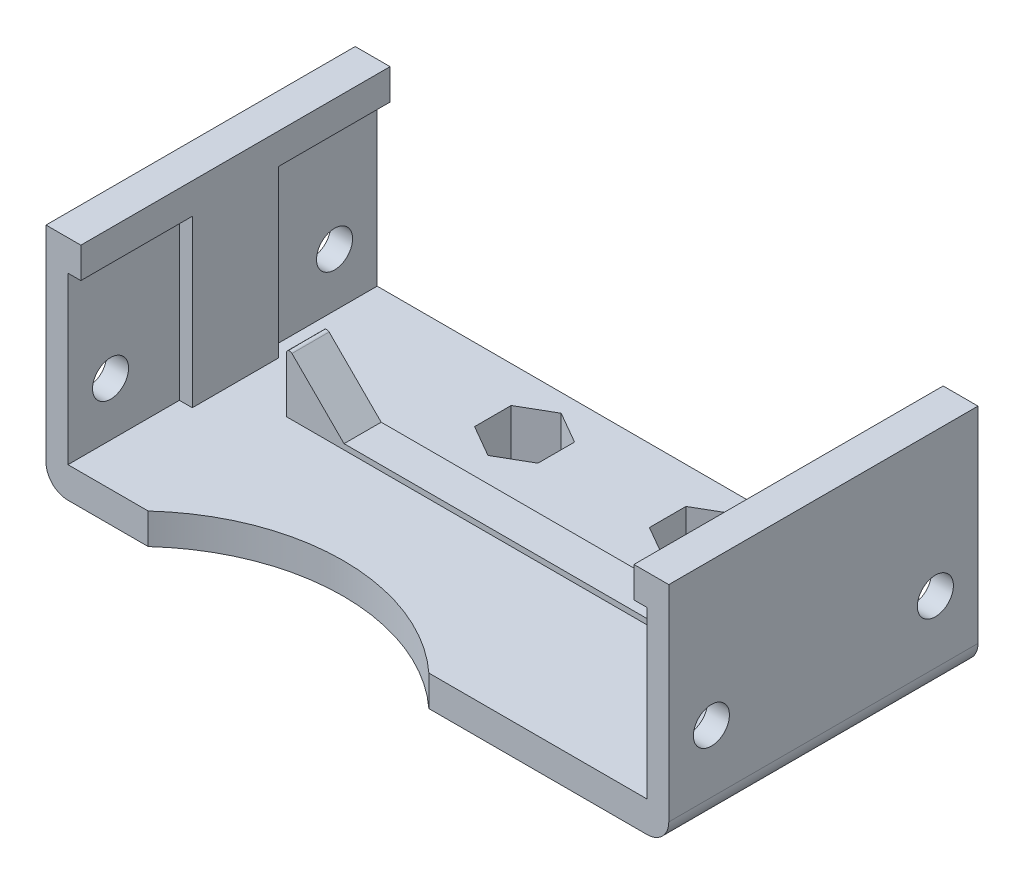
SolidWorks part; units mm, degrees
ref_plane "Front Plane" through (0, 0, 0) normal (0, 0, 1) x (1, 0, 0)
ref_plane "Top Plane" through (0, 0, 0) normal (0, 1, 0) x (1, 0, 0)
ref_plane "Right Plane" through (0, 0, 0) normal (1, 0, 0) x (0, 0, -1)
sketch "Sketch1" plane through (0, 0, 0) normal (0, 0, 1) x (1, 0, 0)
  line L0 (0, 20.81) -> (3.19, 20.81)
  line L1 (0, 20.81) -> (0, 2)
  line L2 (2, 0) -> (55, 0)
  line L3 (57, 20.81) -> (57, 2)
  line L18 (53.81, 20.81) -> (57, 20.81)
  line L54 (53.81, 2.82) -> (53.81, 20.81)
  line L55 (3.19, 20.81) -> (3.19, 2.82)
  line L57 (3.19, 2.82) -> (53.81, 2.82)
  arc A0 (55, 0) -> (57, 2) centre (55, 2) ccw
  arc A1 (0, 2) -> (2, 0) centre (2, 2) ccw
extrude "Boss-Extrude1" add sketch "Sketch1" along normal blind 28.3
sketch "Sketch2" plane through (0, 0, 0) normal (0, 0, 1) x (1, 0, 0)
  line L0 (2.01, 18) -> (54.99, 18)
  line L1 (2.01, 18) -> (2.01, 2.82)
  line L2 (2.01, 2.82) -> (54.99, 2.82)
  line L3 (54.99, 18) -> (54.99, 2.82)
extrude "Cut-Extrude1" cut sketch "Sketch2" along normal blind 10.2
extrude "Cut-Extrude2" cut sketch "Sketch2<2>" against normal blind 10.2 from surface starting at face at (28.5, 9.2052, 28.3)
sketch "Sketch2<2>" plane through (0, 0, 0) normal (0, 0, 1) x (1, 0, 0) same geometry as "Sketch2"
sketch "Sketch3" plane through (0, 0, 0) normal (-1, 0, 0) x (0, 0, 1)
  circle A0 centre (3.9, 7.71) radius 1.65
  circle A1 centre (24.4, 7.71) radius 1.65
extrude "Cut-Extrude3" cut sketch "Sketch3" against normal up to surface (57 mm away) up to face at (57, 11.405, 14.15)
sketch "Sketch4" plane through (0, 0, 0) normal (0, 0, 1) x (1, 0, 0)
  line L0 (8.7121, 8.086) -> (13.4782, 3.32)
  line L3 (8.2, 2.82) -> (48.8, 2.82)
  line L5 (13.4782, 3.32) -> (43.5218, 3.32)
  line L6 (43.5218, 3.32) -> (48.2879, 8.086)
  line L12 (8.2, 2.82) -> (8.2, 7.8739)
  line L13 (48.8, 2.82) -> (48.8, 7.8739)
  arc A0 (48.8, 7.8739) -> (48.2879, 8.086) centre (48.5, 7.8739) ccw
  arc A1 (8.2, 7.8739) -> (8.7121, 8.086) centre (8.5, 7.8739) cw
extrude "Boss-Extrude2" add sketch "Sketch4" along normal blind 3.4 from offset 11.1
sketch "Sketch5" plane through (0, 0, 0) normal (0, -1, 0) x (1, 0, 0)
  line L4 (35.0452, 28.3) -> (9.3548, 28.3)
  arc A0 (9.3548, 28.3) -> (35.0452, 28.3) centre (22.2, 42.3) ccw
extrude "Cut-Extrude4" cut sketch "Sketch5" against normal up to surface (2.82 mm away) up to face at (28.5, 2.82, 12.8)
sketch "Sketch6" plane through (0, 0, 0) normal (0, -1, 0) x (1, 0, 0)
  line L23 (25.9848, 5.5) -> (23.6754, 9.5)
  line L24 (22.8094, 10) -> (18.1906, 10)
  line L25 (17.3246, 9.5) -> (15.0152, 5.5)
  line L26 (15.0152, 4.5) -> (17.3246, 0.5)
  line L27 (18.1906, 0) -> (22.8094, 0)
  line L28 (23.6754, 0.5) -> (25.9848, 4.5)
  line L29 (41.9848, 5.5) -> (39.6754, 9.5)
  line L30 (38.8094, 10) -> (34.1906, 10)
  line L31 (33.3246, 9.5) -> (31.0152, 5.5)
  line L32 (31.0152, 4.5) -> (33.3246, 0.5)
  line L33 (34.1906, 0) -> (38.8094, 0)
  line L34 (39.6754, 0.5) -> (41.9848, 4.5)
  circle A6 centre (20.5, 5) radius 1.65
  circle A7 centre (36.5, 5) radius 1.65
  arc A10 (33.3246, 0.5) -> (34.1906, 0) centre (34.1906, 1) ccw
  arc A11 (38.8094, 0) -> (39.6754, 0.5) centre (38.8094, 1) ccw
  arc A12 (41.9848, 5.5) -> (41.9848, 4.5) centre (41.1188, 5) cw
  arc A13 (39.6754, 9.5) -> (38.8094, 10) centre (38.8094, 9) ccw
  arc A14 (34.1906, 10) -> (33.3246, 9.5) centre (34.1906, 9) ccw
  arc A15 (31.0152, 5.5) -> (31.0152, 4.5) centre (31.8812, 5) ccw
  arc A16 (15.0152, 5.5) -> (15.0152, 4.5) centre (15.8812, 5) ccw
  arc A17 (18.1906, 10) -> (17.3246, 9.5) centre (18.1906, 9) ccw
  arc A18 (23.6754, 9.5) -> (22.8094, 10) centre (22.8094, 9) ccw
  arc A19 (25.9848, 5.5) -> (25.9848, 4.5) centre (25.1188, 5) cw
  arc A20 (22.8094, 0) -> (23.6754, 0.5) centre (22.8094, 1) ccw
  arc A21 (17.3246, 0.5) -> (18.1906, 0) centre (18.1906, 1) ccw
extrude "Boss-Extrude3" add sketch "Sketch6" along normal blind 6
sketch "Sketch8" plane through (0, -6, 0) normal (0, -1, 0) x (1, 0, 0)
  line L0 (23.4, 6.6743) -> (20.5, 8.3486)
  line L7 (20.5, 8.3486) -> (17.6, 6.6743)
  line L8 (17.6, 6.6743) -> (17.6, 3.3257)
  line L21 (17.6, 3.3257) -> (20.5, 1.6514)
  line L22 (20.5, 1.6514) -> (23.4, 3.3257)
  line L23 (23.4, 3.3257) -> (23.4, 6.6743)
  line L25 (39.4, 6.6743) -> (36.5, 8.3486)
  line L26 (36.5, 8.3486) -> (33.6, 6.6743)
  line L27 (33.6, 6.6743) -> (33.6, 3.3257)
  line L28 (33.6, 3.3257) -> (36.5, 1.6514)
  line L29 (36.5, 1.6514) -> (39.4, 3.3257)
  line L30 (39.4, 3.3257) -> (39.4, 6.6743)
extrude "Cut-Extrude5" cut sketch "Sketch8" against normal up to surface (8.82 mm away) from offset 3 up to face at (28.5, 2.82, 12.8) offset against normal yes
